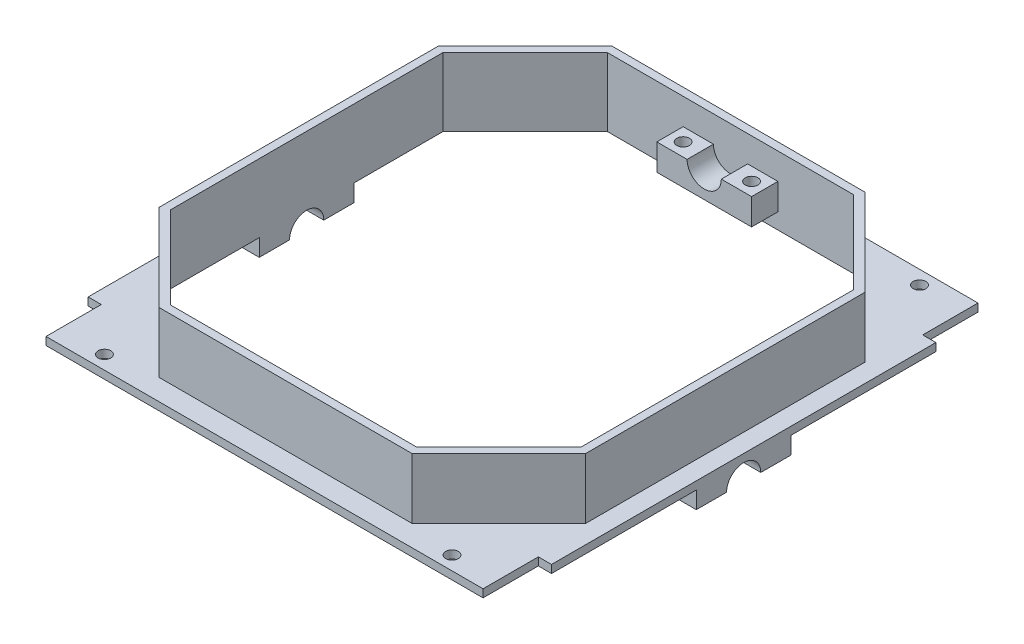
SolidWorks part; units mm, degrees
ref_plane "Front Plane" through (0, 0, 0) normal (0, 0, 1) x (1, 0, 0)
ref_plane "Top Plane" through (0, 0, 0) normal (0, 1, 0) x (1, 0, 0)
ref_plane "Right Plane" through (0, 0, 0) normal (1, 0, 0) x (0, 0, -1)
sketch "Sketch1" plane through (0, 0, 0) normal (0, 1, 0) x (1, 0, 0)
  line L5 (-44, -46.5) -> (44, -46.5)
  line L6 (-44, -46.5) -> (-44, 46.5)
  line L7 (-44, 46.5) -> (44, 46.5)
  line L8 (44, -46.5) -> (44, 46.5)
  line L9 (-44, -46.5) -> (44, 46.5) construction
  line L10 (-44, 46.5) -> (44, -46.5) construction
  point P0 (0, 0)
  dimension "D1" = 88
  dimension "D2" = 93
extrude "Boss-Extrude1" add sketch "Sketch1" along normal blind 13
sketch "Sketch2" plane through (0, 13, 0) normal (0, 1, 0) x (1, 0, 0)
  line L0 (0, 46.5) -> (0, -46.5) construction
  line L1 (-44, -46.5) -> (44, -46.5) construction
  line L2 (-44, 0) -> (44, 0) construction
  line L3 (44, -46.5) -> (44, 46.5) construction
  line L4 (-24, -43) -> (-40.5, -26.5)
  line L5 (-44, 46.5) -> (-44, -46.5) construction
  line L6 (-44, -36.5) -> (-44, -46.5)
  line L7 (-44, -46.5) -> (-34, -46.5)
  line L11 (-24, -43) -> (24, -43)
  line L14 (-34, -46.5) -> (34, -46.5)
  line L15 (-40.5, -26.5) -> (-40.5, 26.5)
  line L17 (-44, -36.5) -> (-44, 36.5)
  line L18 (44, -36.5) -> (44, 36.5)
  line L19 (40.5, -26.5) -> (40.5, 26.5)
  line L20 (44, -46.5) -> (34, -46.5)
  line L21 (44, -36.5) -> (44, -46.5)
  line L22 (24, -43) -> (40.5, -26.5)
  line L23 (24, 43) -> (40.5, 26.5)
  line L24 (44, 36.5) -> (44, 46.5)
  line L25 (44, 46.5) -> (34, 46.5)
  line L26 (-34, 46.5) -> (34, 46.5)
  line L27 (-24, 43) -> (24, 43)
  line L28 (-44, 46.5) -> (-34, 46.5)
  line L29 (-44, 36.5) -> (-44, 46.5)
  line L30 (-24, 43) -> (-40.5, 26.5)
  point P6 (0, 0)
  point P12 (0, 0)
  point P29 (0, -43)
  point P35 (40.5, 0)
  point P37 (-40.5, 0)
  point P40 (0, 43)
  dimension "D1" = 45
  dimension "D2" = 10
  dimension "D3" = 10
  dimension "D4" = 3.5
  dimension "D5" = 3.5
  dimension "D6" = 20
extrude "Cut-Extrude1" cut sketch "Sketch2" against normal offset from surface (11.5 mm away) 1.5 up to face at (0, 0, 0)
sketch "Sketch3" plane through (0, 13, 0) normal (0, 1, 0) x (1, 0, 0)
  line L16 (-23.3787, -41.5) -> (23.3787, -41.5)
  line L17 (23.3787, -41.5) -> (39, -25.8787)
  line L18 (39, -25.8787) -> (39, 25.8787)
  line L19 (39, 25.8787) -> (23.3787, 41.5)
  line L20 (23.3787, 41.5) -> (-23.3787, 41.5)
  line L21 (-23.3787, 41.5) -> (-39, 25.8787)
  line L22 (-39, 25.8787) -> (-39, -25.8787)
  line L23 (-39, -25.8787) -> (-23.3787, -41.5)
  line L24 (-23.3787, -41.5) -> (23.3787, -41.5)
  line L25 (23.3787, -41.5) -> (39, -25.8787)
  line L26 (39, -25.8787) -> (39, 25.8787)
  line L27 (39, 25.8787) -> (23.3787, 41.5)
  line L28 (23.3787, 41.5) -> (-23.3787, 41.5)
  line L29 (-23.3787, 41.5) -> (-39, 25.8787)
  line L30 (-39, 25.8787) -> (-39, -25.8787)
  line L31 (-39, -25.8787) -> (-23.3787, -41.5)
  dimension "D1" = 1.5
extrude "Cut-Extrude2" cut sketch "Sketch3" against normal through all
sketch "Sketch4" plane through (0, 0, -41.5) normal (0, 0, 1) x (1, 0, 0)
  line L0 (0, 0) -> (0, 8) construction
  line L1 (23.3787, 0) -> (-23.3787, 0) construction
  line L2 (3.25, 8) -> (9, 8)
  line L5 (3.25, 8) -> (-3.25, 8) construction
  line L8 (-9, 3) -> (9, 3)
  line L9 (9, 3) -> (9, 8)
  line L10 (23.3787, 13) -> (-23.3787, 13) construction
  line L11 (-9, 3) -> (-9, 8)
  line L12 (-3.25, 8) -> (-9, 8)
  arc A0 (-3.25, 8) -> (3.25, 8) centre (0, 8) ccw
  point P13 (0, 3)
  dimension "D1" = 3.25
  dimension "D2" = 18
  dimension "D3" = 5
  dimension "D4" = 5
extrude "Boss-Extrude2" add sketch "Sketch4" along normal blind 5
sketch "Sketch5" plane through (39, 0, 0) normal (-1, 0, 0) x (0, 0, 1)
  line L0 (0, 0) -> (0, -3.25) construction
  line L2 (25.8787, 0) -> (-25.8787, 0) construction
  line L3 (3.25, -3.25) -> (9, -3.25)
  line L4 (9, -3.25) -> (9, 0)
  line L6 (-9, -3.25) -> (-9, 0)
  line L7 (-3.25, -3.25) -> (-9, -3.25)
  line L8 (-9, 0) -> (9, 0)
  arc A1 (3.25, -3.25) -> (-3.25, -3.25) centre (0, -3.25) ccw
  line M14 (-25.8787, 0) -> (25.8787, 0)
  dimension "D2" = 3.25
  dimension "D1" = 6.5
  dimension "D3" = 18
extrude "Boss-Extrude5" add sketch "Sketch4<2>" against normal blind 5 from surface starting at face at (0, 6.5, 41.5)
sketch "Sketch4<2>" plane through (0, 0, -41.5) normal (0, 0, 1) x (1, 0, 0) same geometry as "Sketch4"
sketch "Sketch6" plane through (0, 1.5, 0) normal (0, 1, 0) x (1, 0, 0)
  line L0 (-44, 0) -> (44, 0) construction
  line L1 (44, -46.5) -> (41.5, -46.5)
  line L2 (44, -46.5) -> (44, -36.5)
  line L3 (44, -36.5) -> (41.5, -36.5)
  line L4 (41.5, -46.5) -> (41.5, -36.5)
  line L5 (44, -46.5) -> (44, 46.5) construction
  line L6 (0, -46.5) -> (0, 46.5) construction
  line L7 (44, 46.5) -> (-44, 46.5) construction
  line L8 (41.5, 46.5) -> (41.5, 36.5)
  line L9 (44, 36.5) -> (41.5, 36.5)
  line L10 (44, 46.5) -> (44, 36.5)
  line L11 (44, 46.5) -> (41.5, 46.5)
  line L12 (-44, 46.5) -> (-41.5, 46.5)
  line L13 (-44, 46.5) -> (-44, 36.5)
  line L14 (-44, 36.5) -> (-41.5, 36.5)
  line L15 (-41.5, 46.5) -> (-41.5, 36.5)
  line L16 (-41.5, -46.5) -> (-41.5, -36.5)
  line L17 (-44, -36.5) -> (-41.5, -36.5)
  line L18 (-44, -46.5) -> (-44, -36.5)
  line L19 (-44, -46.5) -> (-41.5, -46.5)
  point P12 (0, 0)
  point P17 (0, 0)
  dimension "D1" = 2.5
  dimension "D2" = 10
extrude "Cut-Extrude3" cut sketch "Sketch6" against normal through all
sketch "Sketch8" plane through (0, 0, -46.5) normal (0, 0, -1) x (-1, 0, 0)
  line L4 (-41.5, 0) -> (41.5, 0)
  line L5 (41.5, 0) -> (41.5, 1.5)
  line L6 (41.5, 1.5) -> (-41.5, 1.5)
  line L7 (-41.5, 1.5) -> (-41.5, 0)
  line L8 (-41.5, 0) -> (41.5, 0)
  line L9 (41.5, 0) -> (41.5, 1.5)
  line L10 (41.5, 1.5) -> (-41.5, 1.5)
  line L11 (-41.5, 1.5) -> (-41.5, 0)
  dimension "D1" = 0
extrude "Boss-Extrude6" add sketch "Sketch8" along normal blind 0.5
mirror "Mirror1" about plane through (0, 0, 0) normal (0, 0, 1) of "Boss-Extrude6"
sketch "Sketch9" plane through (0, 0, 0) normal (0, 1, 0) x (1, 0, 0)
  line L0 (41.5, -36.5) -> (41.5, -47) construction
  line L1 (-41.5, -47) -> (41.5, -47) construction
  line L2 (-44, 0) -> (44, 0) construction
  line L3 (44, -36.5) -> (44, 36.5) construction
  line L4 (0, -47) -> (0, 47) construction
  line L5 (-41.5, 47) -> (41.5, 47) construction
  circle A0 centre (33, -44.4) radius 1.2
  circle A1 centre (33, 44.4) radius 1.2
  circle A2 centre (-33, 44.4) radius 1.2
  circle A3 centre (-33, -44.4) radius 1.2
  point P12 (0, 0)
  point P18 (0, 0)
  dimension "D1" = 8.5
  dimension "D2" = 2.6
  dimension "D3" = 2.4
extrude "Cut-Extrude4" cut sketch "Sketch9" along normal through all
extrude "Boss-Extrude7" add sketch "Sketch5" against normal up to surface (5 mm away) contours A1 L6 L7 M14 | A1 L3 L4 L8 region at (39, -1.5277, 5.7355) region at (39, -1.5277, -5.7355) up to face at (44, 0.75, 0)
extrude "Boss-Extrude8" add sketch "Sketch5<4>" along normal up to surface (83 mm away) from surface contours A1 L6 L7 M14 | A1 L3 L4 L8 region at (39, -1.5277, 5.7355) region at (39, -1.5277, -5.7355) up to face at (-44, 0.75, 0) starting at face at (-39, 6.5, 0)
sketch "Sketch5<4>" plane through (39, 0, 0) normal (-1, 0, 0) x (0, 0, 1) same geometry as "Sketch5"
sketch "Sketch10" plane through (0, 0, 0) normal (0, 1, 0) x (1, 0, 0)
  circle A0 centre (-6.5, -39) radius 1.2 construction
  circle A1 centre (6.5, -39) radius 1.2 construction
  circle A2 centre (6.5, 39) radius 1.2 construction
  circle A3 centre (-6.5, 39) radius 1.2 construction
  circle A4 centre (-6.5, -39) radius 1.2
  circle A5 centre (6.5, -39) radius 1.2
  circle A6 centre (6.5, 39) radius 1.2
  circle A7 centre (-6.5, 39) radius 1.2
extrude "Cut-Extrude5" cut sketch "Sketch10" along normal through all
sketch "Sketch11" plane through (0, 0, 0) normal (0, 1, 0) x (1, 0, 0)
  circle A0 centre (41.5, -6.5) radius 1.2 construction
  circle A1 centre (41.5, 6.5) radius 1.2 construction
  circle A2 centre (-41.5, -6.5) radius 1.2 construction
  circle A3 centre (-41.5, 6.5) radius 1.2 construction
  circle A4 centre (41.5, -6.5) radius 1.2
  circle A5 centre (41.5, 6.5) radius 1.2
  circle A6 centre (-41.5, -6.5) radius 1.2
  circle A7 centre (-41.5, 6.5) radius 1.2
extrude "Cut-Extrude6" cut sketch "Sketch11" against normal through all
